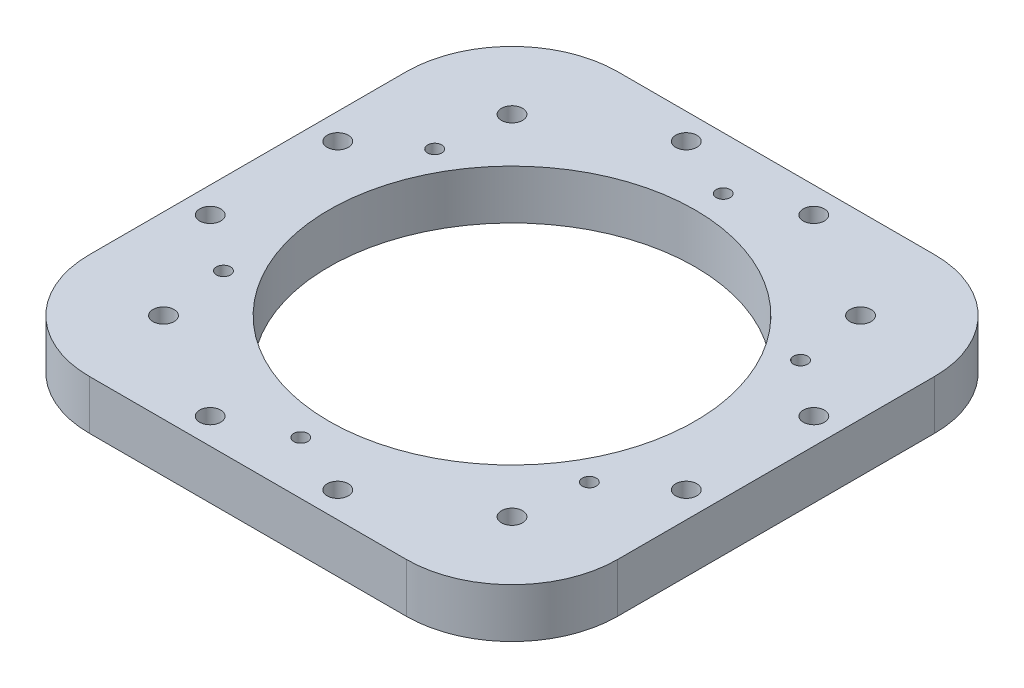
SolidWorks part; units mm, degrees
ref_plane "Front Plane" through (0, 0, 0) normal (0, 0, 1) x (1, 0, 0)
ref_plane "Top Plane" through (0, 0, 0) normal (0, 1, 0) x (1, 0, 0)
ref_plane "Right Plane" through (0, 0, 0) normal (1, 0, 0) x (0, 0, -1)
sketch "Sketch1" plane through (0, 0, 0) normal (0, 1, 0) x (1, 0, 0)
  line L0 (-53.2191, 0) -> (0, 0) construction
  line L1 (0, 0) -> (-55.1529, -14.7782) construction
  line L2 (-37.5, 37.5) -> (37.5, 37.5)
  line L3 (-37.5, 37.5) -> (-37.5, -37.5)
  line L4 (37.5, 37.5) -> (37.5, -37.5)
  line L5 (-37.5, -37.5) -> (37.5, -37.5)
  circle A0 centre (0, 0) radius 37.5 construction
  circle A1 centre (0, 0) radius 30 construction
  circle A2 centre (0, 0) radius 26
  circle A3 centre (0, 30) radius 1
  circle A4 centre (25.9808, 15) radius 1
  circle A5 centre (25.9808, -15) radius 1
  circle A6 centre (0, -30) radius 1
  circle A7 centre (-25.9808, -15) radius 1
  circle A8 centre (-25.9808, 15) radius 1
  circle A9 centre (0, 0) radius 35 construction
  circle A10 centre (-33.8074, -9.0587) radius 1.5
  circle A11 centre (-33.8074, 9.0587) radius 1.5
  circle A12 centre (-24.7487, 24.7487) radius 1.5
  circle A13 centre (-9.0587, 33.8074) radius 1.5
  circle A14 centre (9.0587, 33.8074) radius 1.5
  circle A15 centre (24.7487, 24.7487) radius 1.5
  circle A16 centre (33.8074, 9.0587) radius 1.5
  circle A17 centre (33.8074, -9.0587) radius 1.5
  circle A18 centre (24.7487, -24.7487) radius 1.5
  circle A19 centre (9.0587, -33.8074) radius 1.5
  circle A20 centre (-9.0587, -33.8074) radius 1.5
  circle A21 centre (-24.7487, -24.7487) radius 1.5
  point P19 (0, 0)
  point P47 (0, 0)
  dimension "D1" = 75
  dimension "D2" = 52
  dimension "D3" = 60
  dimension "D4" = 2
  dimension "D7" = 70
  dimension "D8" = 3
  dimension "D6" = 15
  dimension "D5" = 6
  dimension "D9" = 12
extrude "Boss-Extrude1" add sketch "Sketch1" along normal blind 7
fillet "Fillet1" radius 15 4 edges at (-37.5, 3.5, -37.5) (-37.5, 3.5, 37.5) (37.5, 3.5, 37.5) (37.5, 3.5, -37.5)
